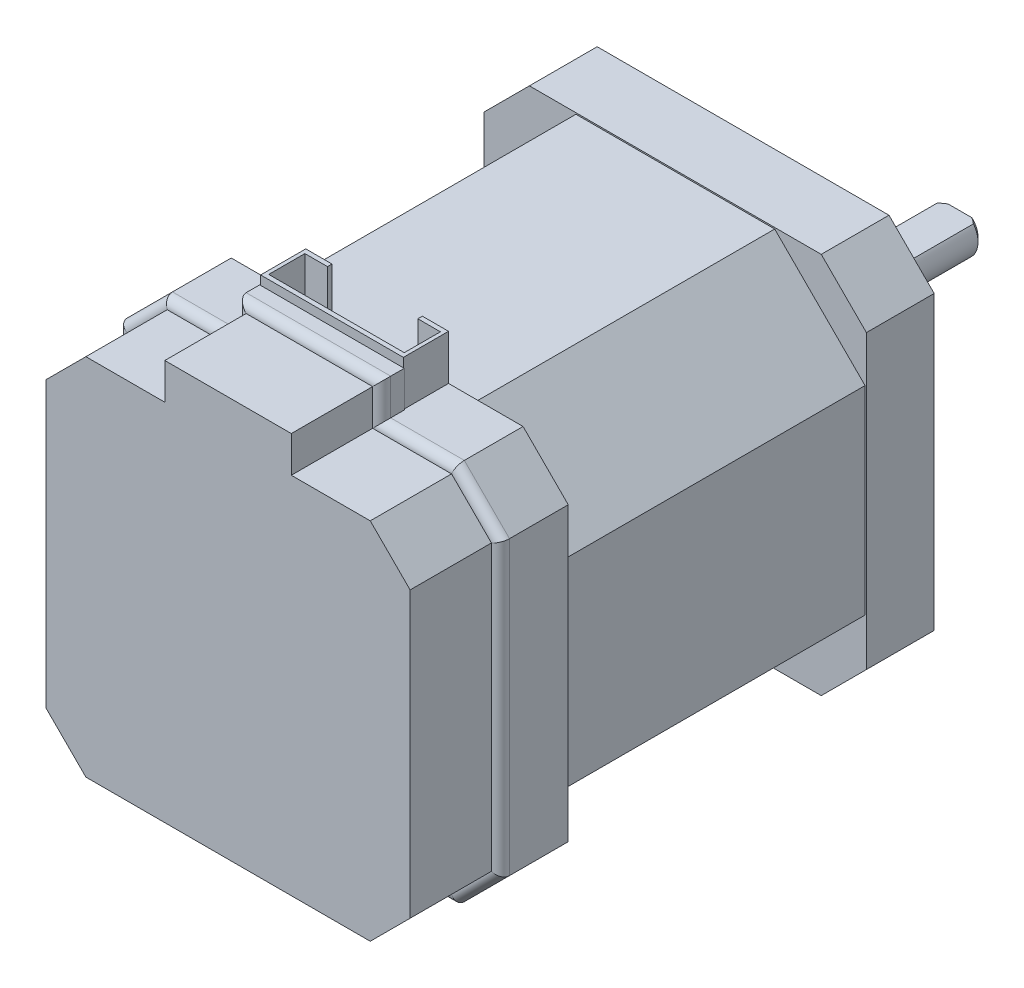
SolidWorks part; units mm, degrees
ref_plane "前视基准面" through (0, 0, 0) normal (0, 0, 1) x (1, 0, 0)
ref_plane "上视基准面" through (0, 0, 0) normal (0, 1, 0) x (1, 0, 0)
ref_plane "右视基准面" through (0, 0, 0) normal (1, 0, 0) x (0, 0, -1)
sketch "草图1" plane through (0, 0, 0) normal (0, 0, 1) x (1, 0, 0)
  line L1 (-21, 21) -> (21, 21)
  line L2 (-21, 21) -> (-21, -21)
  line L3 (-21, -21) -> (21, -21)
  line L4 (21, 21) -> (21, -21)
  line L5 (-21, 21) -> (21, -21) construction
  line L6 (-21, -21) -> (21, 21) construction
  line L11 (-15.5, 15.5) -> (15.5, -15.5) construction
  line L12 (-15.5, -15.5) -> (15.5, 15.5) construction
  point P0 (0, 0)
  point P5 (0, 0)
  dimension "D1" = 42
  dimension "D2" = 42
extrude "凸台-拉伸1" add sketch "草图1" along normal blind 33
chamfer "倒角1" distance 10 angle 45 4 edges at (-21, -21, 16.5) (21, -21, 16.5) (21, 21, 16.5) (-21, 21, 16.5)
sketch "草图2" plane through (0, 0, 33) normal (0, 0, 1) x (1, 0, 0)
  line L1 (-21.15, 21.15) -> (21.15, 21.15)
  line L2 (-21.15, 21.15) -> (-21.15, -21.15)
  line L3 (-21.15, -21.15) -> (21.15, -21.15)
  line L4 (21.15, 21.15) -> (21.15, -21.15)
  line L5 (-21.15, 21.15) -> (21.15, -21.15) construction
  line L6 (-21.15, -21.15) -> (21.15, 21.15) construction
  point P0 (0, 0)
  dimension "D1" = 42.3
  dimension "D2" = 42.3
extrude "凸台-拉伸2" add sketch "草图2" along normal blind 7.5
sketch "草图3" plane through (0, 0, 0) normal (0, 0, -1) x (-1, 0, 0)
  line L5 (-21.15, 21.15) -> (21.15, 21.15)
  line L6 (-21.15, 21.15) -> (-21.15, -21.15)
  line L7 (-21.15, -21.15) -> (21.15, -21.15)
  line L8 (21.15, 21.15) -> (21.15, -21.15)
  line L9 (-21.15, 21.15) -> (21.15, -21.15) construction
  line L10 (-21.15, -21.15) -> (21.15, 21.15) construction
  point P0 (0, 0)
  point P1 (0, 0)
extrude "凸台-拉伸3" add sketch "草图3" along normal blind 7.5
chamfer "倒角2" distance 5 angle 45 8 edges at (-21.15, -21.15, -3.75) (-21.15, -21.15, 36.75) (21.15, -21.15, 36.75) (21.15, -21.15, -3.75) (21.15, 21.15, -3.75) (21.15, 21.15, 36.75) (-21.15, 21.15, 36.75) (-21.15, 21.15, -3.75)
sketch "草图4" plane through (0, 0, -7.5) normal (0, 0, -1) x (-1, 0, 0)
  line L1 (-15.5, 15.5) -> (15.5, 15.5) construction
  line L2 (-15.5, 15.5) -> (-15.5, -15.5) construction
  line L3 (-15.5, -15.5) -> (15.5, -15.5) construction
  line L4 (15.5, 15.5) -> (15.5, -15.5) construction
  line L5 (-15.5, 15.5) -> (15.5, -15.5) construction
  line L6 (-15.5, -15.5) -> (15.5, 15.5) construction
  circle A0 centre (-15.5, 15.5) radius 1.5
  circle A1 centre (15.5, 15.5) radius 1.5
  circle A2 centre (15.5, -15.5) radius 1.5
  circle A3 centre (-15.5, -15.5) radius 1.5
  point P0 (0, 0)
extrude "切除-拉伸1" cut sketch "草图4" against normal blind 4.5
sketch "草图5" plane through (0, 0, -7.5) normal (0, 0, -1) x (-1, 0, 0)
  circle A0 centre (0, 0) radius 11
  circle A1 centre (0, 0) radius 3.75
extrude "凸台-拉伸4" add sketch "草图5" along normal blind 2
sketch "草图6" plane through (0, 0, -7.5) normal (0, 0, -1) x (-1, 0, 0)
  circle A0 centre (0, 0) radius 2.5
extrude "凸台-拉伸5" add sketch "草图6" along normal blind 24
sketch "草图7" plane through (0, 0, -31.5) normal (0, 0, -1) x (-1, 0, 0)
  line L3 (2, 1.5) -> (-2, 1.5)
  arc A0 (2, 1.5) -> (-2, 1.5) centre (0, 0) ccw
extrude "切除-拉伸2" cut sketch "草图7" against normal blind 19
chamfer "倒角3" distance 0.5 angle 45 1 edges at (0, -2.5, -31.5)
sketch "草图8" plane through (0, 0, 40.5) normal (0, 0, 1) x (1, 0, 0)
  line L0 (0, 21.15) -> (-8, 21.15)
  line L1 (16.15, 21.15) -> (-16.15, 21.15) construction
  line L2 (-8, 21.15) -> (-8, 25.15)
  line L3 (-8, 25.15) -> (8, 25.15)
  line L4 (8, 25.15) -> (8, 21.15)
  line L5 (8, 21.15) -> (0, 21.15)
extrude "凸台-拉伸6" add sketch "草图8" against normal blind 2.5
fillet "圆角1" radius 1 12 edges at (-18.65, 18.65, 40.5) (-12.075, 21.15, 40.5) (-8, 23.15, 40.5) (0, 25.15, 40.5) (8, 23.15, 40.5) (12.075, 21.15, 40.5) (18.65, 18.65, 40.5) (21.15, 0, 40.5) (18.65, -18.65, 40.5) (0, -21.15, 40.5) (-18.65, -18.65, 40.5) (-21.15, 0, 40.5)
sketch "草图9" plane through (0, 21.15, 0) normal (0, 1, 0) x (1, 0, 0)
  line L5 (7.9, -33) -> (5, -33)
  line L6 (-7.9, -38) -> (7.9, -38)
  line L7 (-7.5, -37.5) -> (-7.5, -33.5)
  line L8 (7.5, -33.5) -> (5, -33.5)
  line L9 (7.5, -37.5) -> (7.5, -33.5)
  line L10 (-7.5, -37.5) -> (7.5, -37.5)
  line L13 (-5, -33) -> (-5, -33.5)
  line L14 (5, -33) -> (5, -33.5)
  line L15 (-5, -33) -> (-7.9, -33)
  line L16 (8, -33) -> (-8, -33) construction
  line L17 (-5, -33.5) -> (-7.5, -33.5)
  line L18 (7.5, -33.5) -> (-7.5, -33.5) construction
  line L19 (-8, -38) -> (8, -38) construction
  line L20 (-7.9, -33) -> (-7.9, -38)
  line L22 (-8, -38) -> (-8, -33) construction
  line L23 (7.9, -33) -> (7.9, -38)
  line L25 (8, -38) -> (8, -33) construction
  dimension "D1" = 0.5
extrude "凸台-拉伸7" add sketch "草图9" along normal blind 5
sketch "草图10" plane through (0, 0, 40.5) normal (0, 0, 1) x (1, 0, 0)
  line L12 (-7, 20.15) -> (-15.7358, 20.15)
  line L13 (-15.7358, 20.15) -> (-20.15, 15.7358)
  line L14 (-20.15, 15.7358) -> (-20.15, -15.7358)
  line L15 (-20.15, -15.7358) -> (-15.7358, -20.15)
  line L16 (-15.7358, -20.15) -> (15.7358, -20.15)
  line L17 (15.7358, -20.15) -> (20.15, -15.7358)
  line L18 (20.15, -15.7358) -> (20.15, 15.7358)
  line L19 (20.15, 15.7358) -> (15.7358, 20.15)
  line L20 (15.7358, 20.15) -> (7, 20.15)
  line L21 (7, 20.15) -> (7, 24.15)
  line L22 (7, 24.15) -> (-7, 24.15)
  line L23 (-7, 24.15) -> (-7, 20.15)
  line L24 (-7, 20.15) -> (-15.7358, 20.15)
  line L25 (-15.7358, 20.15) -> (-20.15, 15.7358)
  line L26 (-20.15, 15.7358) -> (-20.15, -15.7358)
  line L27 (-20.15, -15.7358) -> (-15.7358, -20.15)
  line L28 (-15.7358, -20.15) -> (15.7358, -20.15)
  line L29 (15.7358, -20.15) -> (20.15, -15.7358)
  line L30 (20.15, -15.7358) -> (20.15, 15.7358)
  line L31 (20.15, 15.7358) -> (15.7358, 20.15)
  line L32 (15.7358, 20.15) -> (7, 20.15)
  line L33 (7, 20.15) -> (7, 24.15)
  line L34 (7, 24.15) -> (-7, 24.15)
  line L35 (-7, 24.15) -> (-7, 20.15)
  dimension "D1" = 0
extrude "凸台-拉伸8" add sketch "草图10" along normal blind 9
chamfer "倒角4" distance 2.5 angle 45 1 edges at (-2.5, 0, -7.5)
